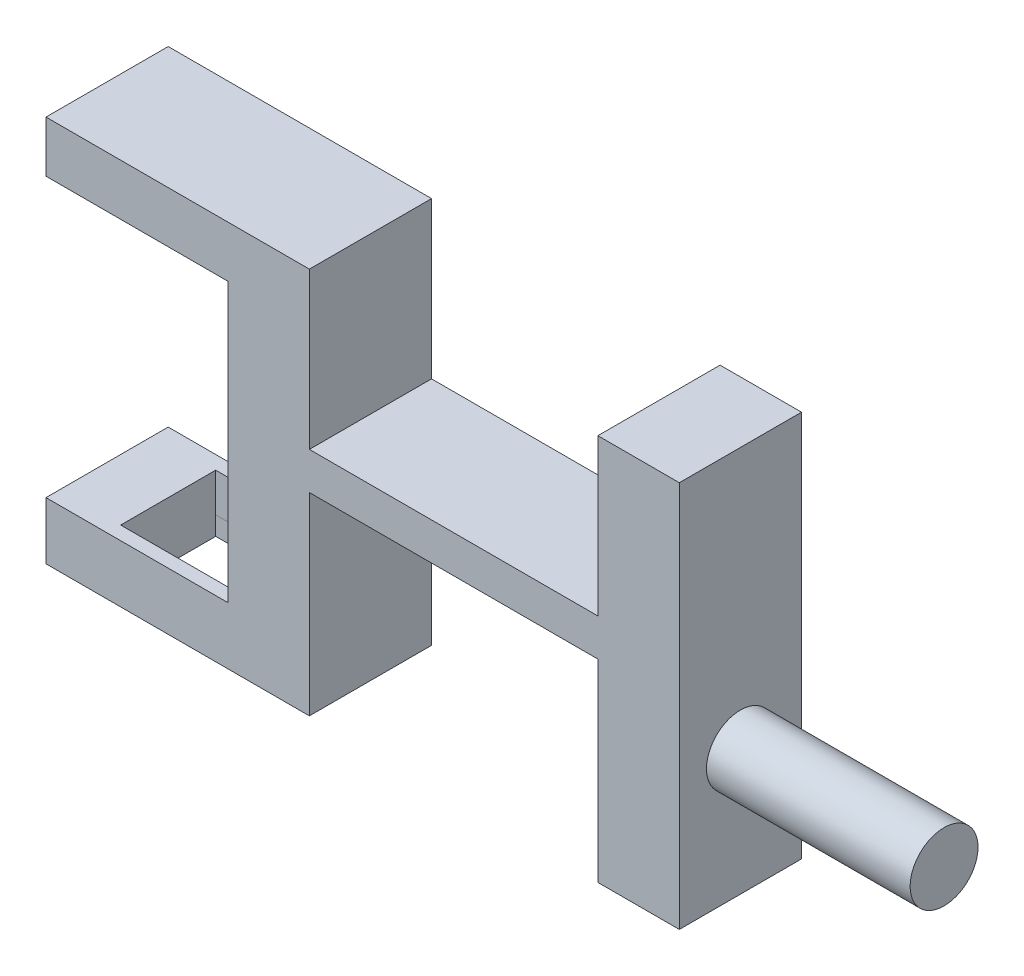
SolidWorks part; units mm, degrees
ref_plane "Front Plane" through (0, 0, 0) normal (0, 0, 1) x (1, 0, 0)
ref_plane "Top Plane" through (0, 0, 0) normal (0, 1, 0) x (1, 0, 0)
ref_plane "Right Plane" through (0, 0, 0) normal (1, 0, 0) x (0, 0, -1)
sketch "Sketch2" plane through (0, 0, 0) normal (0, 0, 1) x (1, 0, 0)
  line L0 (0, -55) -> (0, 55) construction
  line L1 (0, 55) -> (66.5, 55)
  line L2 (0, 55) -> (0, 0)
  line L3 (0, 0) -> (66.5, 0)
  line L4 (66.5, 55) -> (66.5, 0)
  line L5 (55, 0) -> (-55, 0) construction
  line L7 (12, 50.75) -> (54.5, 50.75)
  line L8 (12, 50.75) -> (12, 30.25)
  line L9 (12, 30.25) -> (54.5, 30.25)
  line L10 (54.5, 50.75) -> (54.5, 30.25)
  line L11 (12, 24.75) -> (54.5, 24.75)
  line L12 (12, 24.75) -> (12, 4.25)
  line L13 (12, 4.25) -> (54.5, 4.25)
  line L14 (54.5, 24.75) -> (54.5, 4.25)
  dimension "D1" = 55
  dimension "D2" = 12
  dimension "D3" = 42.5
  dimension "D4" = 20.5
  dimension "D5" = 5.5
  dimension "D6" = 42.5
  dimension "D7" = 20.5
  dimension "D8" = 12
  dimension "D9" = 4.25
  dimension "D10" = 12
extrude "Boss-Extrude1" add sketch "Sketch2" along normal blind 18
sketch "Sketch3" plane through (0, 0, 18) normal (0, 0, 1) x (1, 0, 0)
  line L2 (12, 24.75) -> (12, 4.25) construction
  line L3 (54.5, 24.75) -> (12, 24.75) construction
  circle A8 centre (8.15, 19.75) radius 2.5
  circle A9 centre (8.15, 9.75) radius 2.5
  circle A10 centre (57.85, 9.75) radius 2.5
  circle A11 centre (57.85, 19.75) radius 2.5
  dimension "D9" = 45.85
  dimension "D10" = 45.85
  dimension "D11" = 5
  dimension "D12" = 5
  dimension "D13" = 3.85
  dimension "D14" = 3.85
  dimension "D15" = 10
  dimension "D16" = 5
  dimension "D17" = 5
  dimension "D18" = 5
  dimension "D19" = 5
  dimension "D24" = 10
sketch "Sketch5" plane through (0, 0, 0) normal (-1, 0, 0) x (0, 0, 1)
  line L0 (0, -55) -> (0, 55) construction
  line L1 (0, 55) -> (2, 55)
  line L2 (0, 55) -> (0, 49)
  line L3 (0, 49) -> (2, 49)
  line L4 (2, 55) -> (2, 49)
  line L5 (18, 55) -> (0, 55) construction
  line L6 (55, 0) -> (-55, 0) construction
  line L7 (18, 55) -> (16, 55)
  line L8 (18, 55) -> (18, 49)
  line L9 (18, 49) -> (16, 49)
  line L10 (16, 55) -> (16, 49)
  line L11 (0, 0) -> (2, 0)
  line L12 (0, 0) -> (0, 6)
  line L13 (0, 6) -> (2, 6)
  line L14 (2, 0) -> (2, 6)
  line L15 (18, 0) -> (16, 0)
  line L16 (18, 0) -> (18, 6)
  line L17 (18, 6) -> (16, 6)
  line L18 (16, 0) -> (16, 6)
  line L19 (18, 55) -> (18, 0) construction
  dimension "D1" = 2
  dimension "D2" = 2
  dimension "D3" = 6
  dimension "D4" = 6
  dimension "D5" = 2
  dimension "D6" = 2
  dimension "D7" = 6
  dimension "D8" = 6
extrude "Boss-Extrude2" add sketch "Sketch5" along normal blind 26.8
sketch "Sketch6" plane through (0, 0, 2) normal (0, 0, 1) x (1, 0, 0)
  line L0 (-26.8, 49) -> (0, 49) construction
  line L1 (-23.8, 49) -> (-26.8, 49)
  line L2 (-23.8, 49) -> (-23.8, 55)
  line L3 (-23.8, 55) -> (-26.8, 55)
  line L4 (-26.8, 49) -> (-26.8, 55)
  line L5 (66.5, 55) -> (-26.8, 55) construction
  line L6 (-26.8, 55) -> (-26.8, 49) construction
  line L7 (55, 0) -> (-55, 0) construction
  line L8 (-26.8, 6) -> (-24.8, 6)
  line L9 (-26.8, 6) -> (-26.8, 0)
  line L10 (-26.8, 0) -> (-24.8, 0)
  line L11 (-24.8, 6) -> (-24.8, 0)
  dimension "D1" = 3
  dimension "D2" = 2
extrude "Boss-Extrude3" add sketch "Sketch6" along normal up to next
sketch "Sketch8" plane through (0, 0, 18) normal (0, 0, 1) x (1, 0, 0)
  line L0 (66.5, 55) -> (-26.8, 55) construction
  line L1 (12, 50.75) -> (54, 50.75)
  line L2 (12, 50.75) -> (12, 55)
  line L3 (12, 55) -> (54, 55)
  line L4 (54, 50.75) -> (54, 55)
  line L5 (55, 0) -> (-55, 0) construction
  line L6 (12, 4.25) -> (54.5, 4.25)
  line L7 (12, 4.25) -> (12, 0)
  line L8 (12, 0) -> (54.5, 0)
  line L9 (54.5, 4.25) -> (54.5, 0)
extrude "Cut-Extrude3" cut sketch "Sketch8" against normal up to next
sketch "Sketch12" plane through (0, 0, 2) normal (0, 0, 1) x (1, 0, 0)
  line L0 (-26.8, 6) -> (0, 6) construction
  line L1 (-8, 6) -> (-5, 6)
  line L2 (-8, 6) -> (-8, 0)
  line L3 (-8, 0) -> (-5, 0)
  line L4 (-5, 6) -> (-5, 0)
  line L5 (55, 0) -> (-55, 0) construction
  line L6 (0, -55) -> (0, 55) construction
  dimension "D1" = 3
  dimension "D2" = 5
extrude "Boss-Extrude7" add sketch "Sketch12" along normal up to surface (14 mm away) up to face at (-12.4, 3, 16)
sketch "Sketch14" plane through (-8, 0, 0) normal (-1, 0, 0) x (0, 0, 1)
  line L0 (18, 6) -> (0, 6) construction
  line L1 (7, 6) -> (11, 6)
  line L2 (7, 6) -> (7, 0)
  line L3 (7, 0) -> (11, 0)
  line L4 (11, 6) -> (11, 0)
  line L5 (55, 0) -> (-55, 0) construction
  line L6 (0, -55) -> (0, 55) construction
  line L7 (18, 0) -> (18, 6) construction
  dimension "D1" = 7
  dimension "D2" = 7
extrude "Boss-Extrude8" add sketch "Sketch14" along normal up to surface (16.8 mm away) up to face at (-24.8, 3, 9)
sketch "Sketch17" plane through (0, 0, 2) normal (0, 0, 1) x (1, 0, 0)
  line L1 (-23.8, 55) -> (0, 55)
  line L2 (-23.8, 55) -> (-23.8, 49)
  line L3 (-23.8, 49) -> (0, 49)
  line L4 (0, 55) -> (0, 49)
extrude "Boss-Extrude9" add sketch "Sketch17" along normal blind 14 and the other way blind 1
sketch "Sketch18" plane through (0, 6, 0) normal (0, 1, 0) x (1, 0, 0)
  line L1 (-5, -2) -> (-24.8, -2)
  line L2 (-5, -2) -> (-5, -16)
  line L3 (-5, -16) -> (-24.8, -16)
  line L4 (-24.8, -2) -> (-24.8, -16)
extrude "Cut-Extrude4" cut sketch "Sketch18" against normal blind 10
sketch "Sketch20" plane through (0, 6, 0) normal (0, 1, 0) x (1, 0, 0)
  line L0 (-24.8, -16) -> (0, -16) construction
  line L1 (-24.8, -2) -> (-19.8, -2)
  line L2 (-24.8, -2) -> (-24.8, -16)
  line L3 (-24.8, -16) -> (-19.8, -16)
  line L4 (-19.8, -2) -> (-19.8, -16)
  dimension "D1" = 5
extrude "Boss-Extrude10" add sketch "Sketch20" against normal blind 6
sketch "Sketch22" plane through (0, 55, 0) normal (0, 1, 0) x (1, 0, 0)
  line L0 (-55, 0) -> (55, 0) construction
  line L1 (-26.8, -18) -> (12, -18)
  line L2 (-26.8, -18) -> (-26.8, 0)
  line L3 (-26.8, 0) -> (12, 0)
  line L4 (12, -18) -> (12, 0)
  line L5 (12, -18) -> (12, 0) construction
extrude "Boss-Extrude11" add sketch "Sketch22" along normal blind 1
sketch "Sketch23" plane through (0, 49, 0) normal (0, -1, 0) x (1, 0, 0)
  line L1 (0, 18) -> (-26.8, 18)
  line L2 (0, 18) -> (0, 0)
  line L3 (0, 0) -> (-26.8, 0)
  line L4 (-26.8, 18) -> (-26.8, 0)
extrude "Boss-Extrude12" add sketch "Sketch23" along normal blind 1
sketch "Sketch24" plane through (0, 6, 0) normal (0, 1, 0) x (1, 0, 0)
  line L0 (0, 0) -> (-26.8, 0)
  line L1 (-26.8, 0) -> (-26.8, -18)
  line L2 (-26.8, -18) -> (0, -18)
  line L3 (0, -18) -> (0, -16)
  line L4 (0, -16) -> (-19.8, -16)
  line L5 (-19.8, -16) -> (-19.8, -2)
  line L6 (-19.8, -2) -> (0, -2)
  line L7 (0, -2) -> (0, 0)
extrude "Boss-Extrude13" add sketch "Sketch24" along normal blind 1
sketch "Sketch25" plane through (0, 55, 0) normal (0, 1, 0) x (1, 0, 0)
  line L0 (-55, 0) -> (55, 0) construction
  line L1 (66.5, -18) -> (54.5, -18)
  line L2 (66.5, -18) -> (66.5, 0)
  line L3 (66.5, 0) -> (54.5, 0)
  line L4 (54.5, -18) -> (54.5, 0)
  line L5 (54.5, -18) -> (54.5, 0) construction
extrude "Boss-Extrude14" add sketch "Sketch25" along normal blind 1
sketch "Sketch27" plane through (0, 0, 0) normal (0, -1, 0) x (1, 0, 0)
  line L0 (-26.8, 18) -> (12, 18)
  line L1 (12, 18) -> (12, 0)
  line L2 (55, 0) -> (-55, 0) construction
  line L3 (12, 18) -> (12, 0) construction
  line L4 (12, 0) -> (-26.8, 0)
  line L5 (-26.8, 0) -> (-26.8, 18) construction
  line L6 (-26.8, 0) -> (-26.8, 18)
  line L7 (-19.8, 16) -> (-19.8, 2)
  line L8 (-19.8, 2) -> (0, 2)
  line L9 (0, 2) -> (0, 16)
  line L10 (0, 16) -> (0, 2) construction
  line L11 (-19.8, 16) -> (0, 16) construction
  line L12 (0, 16) -> (-19.8, 16)
extrude "Boss-Extrude15" add sketch "Sketch27" along normal blind 1
sketch "Sketch28" plane through (0, 0, 0) normal (0, -1, 0) x (1, 0, 0)
  line L0 (55, 0) -> (-55, 0) construction
  line L1 (54.5, 18) -> (66.5, 18)
  line L2 (54.5, 18) -> (54.5, 0)
  line L3 (54.5, 0) -> (66.5, 0)
  line L4 (66.5, 18) -> (66.5, 0)
  line L5 (66.5, 18) -> (66.5, 0) construction
extrude "Boss-Extrude16" add sketch "Sketch28" along normal blind 1
sketch "Sketch32" plane through (-26.8, 0, 0) normal (-1, 0, 0) x (0, 0, 1)
  line L0 (0, -55) -> (0, 55) construction
  line L1 (18, 7) -> (0, 7)
  line L2 (18, 7) -> (18, 4.25)
  line L3 (18, 4.25) -> (0, 4.25)
  line L4 (0, 7) -> (0, 4.25)
  dimension "D1" = 2.75
extrude "Cut-Extrude8" cut sketch "Sketch32" against normal blind 26.8
sketch "Sketch33" plane through (0, -1, 0) normal (0, -1, 0) x (1, 0, 0)
  line L0 (-26.8, 18) -> (12, 18)
  line L1 (12, 18) -> (12, 0)
  line L2 (55, 0) -> (-55, 0) construction
  line L3 (12, 18) -> (12, 0) construction
  line L4 (12, 0) -> (-26.8, 0)
  line L5 (-26.8, 18) -> (-26.8, 0) construction
  line L6 (-26.8, 0) -> (-26.8, 18)
  line L7 (-19.8, 16) -> (0, 16)
  line L8 (0, -55) -> (0, 55) construction
  line L9 (0, 16) -> (-19.8, 16) construction
  line L10 (0, 16) -> (0, 1.9658)
  line L11 (0, 1.9658) -> (-19.8, 2)
  line L12 (-19.8, 2) -> (-19.8, 16)
extrude "Boss-Extrude17" add sketch "Sketch33" along normal blind 2.75
sketch "Sketch34" plane through (0, -1, 0) normal (0, -1, 0) x (1, 0, 0)
  line L0 (31.9, 0) -> (-31.9, 0) construction
  line L1 (54.5, 18) -> (66.5, 18)
  line L2 (54.5, 18) -> (54.5, 0)
  line L3 (54.5, 0) -> (66.5, 0)
  line L4 (66.5, 18) -> (66.5, 0)
  line L5 (66.5, 0) -> (66.5, 18) construction
extrude "Boss-Extrude18" add sketch "Sketch34" along normal blind 2.75
sketch "Sketch35" plane through (0, 48, 0) normal (0, -1, 0) x (1, 0, 0)
  line L1 (-26.8, 18) -> (0, 18)
  line L2 (-26.8, 18) -> (-26.8, 0)
  line L3 (-26.8, 0) -> (0, 0)
  line L4 (0, 18) -> (0, 0)
extrude "Boss-Extrude19" add sketch "Sketch35" along normal blind 2.3
sketch "Sketch36" plane through (0, 56, 0) normal (0, 1, 0) x (1, 0, 0)
  line L0 (-32.8625, 0) -> (32.8625, 0) construction
  line L1 (66.5, -18) -> (54.5, -18)
  line L2 (66.5, -18) -> (66.5, 0)
  line L3 (66.5, 0) -> (54.5, 0)
  line L4 (54.5, -18) -> (54.5, 0)
  line L5 (54.5, -18) -> (54.5, 0) construction
  line L7 (12, -18) -> (-26.8, -18)
  line L8 (12, -18) -> (12, 0)
  line L9 (12, 0) -> (-26.8, 0)
  line L10 (-26.8, -18) -> (-26.8, 0)
extrude "Cut-Extrude9" cut sketch "Sketch36" against normal blind 2.75
sketch "Sketch37" plane through (-26.8, 0, 0) normal (-1, 0, 0) x (0, 0, 1)
  line L0 (0, 53.25) -> (18, 53.25) construction
  line L1 (0, -32.8625) -> (0, 32.8625) construction
  line L2 (18, 45.7) -> (18, 53.25) construction
  circle A0 centre (4, 49.45) radius 2.5
  circle A1 centre (14, 49.45) radius 2.5
  dimension "D1" = 3.8
  dimension "D2" = 4
  dimension "D3" = 4
  dimension "D4" = 3.8
  dimension "D5" = 5
  dimension "D6" = 5
sketch "Sketch38" plane through (-26.8, 0, 0) normal (-1, 0, 0) x (0, 0, 1)
  line L0 (0, 4.25) -> (18, 4.25) construction
  line L1 (0, -32.8625) -> (0, 32.8625) construction
  line L2 (18, -3.75) -> (18, 4.25) construction
  circle A0 centre (4, 0.45) radius 2.5
  circle A1 centre (14, 0.45) radius 2.5
  dimension "D1" = 3.8
  dimension "D2" = 5
  dimension "D3" = 4
  dimension "D4" = 5
  dimension "D5" = 4
  dimension "D6" = 3.8
extrude "Cut-Extrude10" cut sketch "Sketch37" against normal blind 6
sketch "Sketch39" plane through (0, 0, 0) normal (0, 0, -1) x (-1, 0, 0)
  line L0 (-54.5, 30.25) -> (-54.5, 27.5) construction
  line L2 (-54.5, 27.5) -> (-66.5, 27.5) construction
  line L3 (-66.5, -3.75) -> (-66.5, 53.25) construction
  circle A2 centre (-8.15, 19.75) radius 2.5
  circle A3 centre (-8.15, 9.75) radius 2.5
  circle A6 centre (-57.85, 19.75) radius 2.5
  circle A7 centre (-57.85, 9.75) radius 2.5
  circle A8 centre (-8.15, 45.25) radius 2.5
  circle A9 centre (-8.15, 35.25) radius 2.5
  circle A10 centre (-57.85, 45.25) radius 2.5
  circle A11 centre (-57.85, 35.25) radius 2.5
  dimension "D1" = 2.75
  dimension "D4" = 5
  dimension "D5" = 5
  dimension "D6" = 5
  dimension "D7" = 5
extrude "Cut-Extrude12" cut sketch "Sketch39" against normal blind 10
extrude "Cut-Extrude11" cut sketch "Sketch38" against normal blind 6
sketch "Sketch40" plane through (0, 0, 0) normal (0, 0, -1) x (-1, 0, 0)
  line L0 (-57.85, 35.25) -> (-8.15, 35.25) construction
  line L1 (-57.85, 19.75) -> (-8.15, 19.75) construction
  line L3 (-54, 50.75) -> (-54.5, 50.75)
  line L4 (-54, 50.75) -> (-54, 55)
  line L5 (-54, 55) -> (-54.5, 55)
  line L6 (-54.5, 50.75) -> (-54.5, 55)
extrude "Cut-Extrude13" cut sketch "Sketch40" against normal up to surface (18 mm away) up to face at (25.44, 30.97, 18)
sketch "Sketch43" plane through (0, 4.25, 0) normal (0, 1, 0) x (1, 0, 0)
  line L0 (0, 0) -> (-26.8, 0)
  line L1 (-26.8, 0) -> (-26.8, -18)
  line L2 (-26.8, -18) -> (0, -18)
  line L3 (0, -18) -> (0, -16)
  line L4 (0, -16) -> (-19.8, -16)
  line L5 (-19.8, -16) -> (-19.8, -2)
  line L6 (-19.8, -2) -> (0, -2)
  line L7 (0, -2) -> (0, 0)
extrude "Boss-Extrude21" add sketch "Sketch43" along normal blind 0.45
sketch "Sketch44" plane through (66.5, 0, 0) normal (1, 0, 0) x (0, 0, -1)
  line L0 (0, -3.75) -> (-18, -3.75) construction
  line L1 (-18, -3.75) -> (-18, 53.25) construction
  circle A0 centre (-9, 14.75) radius 5
  dimension "D1" = 10
  dimension "D2" = 18.5
  dimension "D3" = 9
extrude "Boss-Extrude22" add sketch "Sketch44" along normal blind 30
sketch "Sketch45" plane through (-19.8, 0, 0) normal (1, 0, 0) x (0, 0, -1)
  line L1 (-16, 4.7) -> (-2, 4.7)
  line L2 (-16, 4.7) -> (-16, -3.75)
  line L3 (-16, -3.75) -> (-2, -3.75)
  line L4 (-2, 4.7) -> (-2, -3.75)
  line L5 (-16, 4.7) -> (-2, -3.75) construction
  line L6 (-16, -3.75) -> (-2, 4.7) construction
  point P4 (-9, 0.475)
extrude "Boss-Extrude23" add sketch "Sketch45" along normal blind 2
